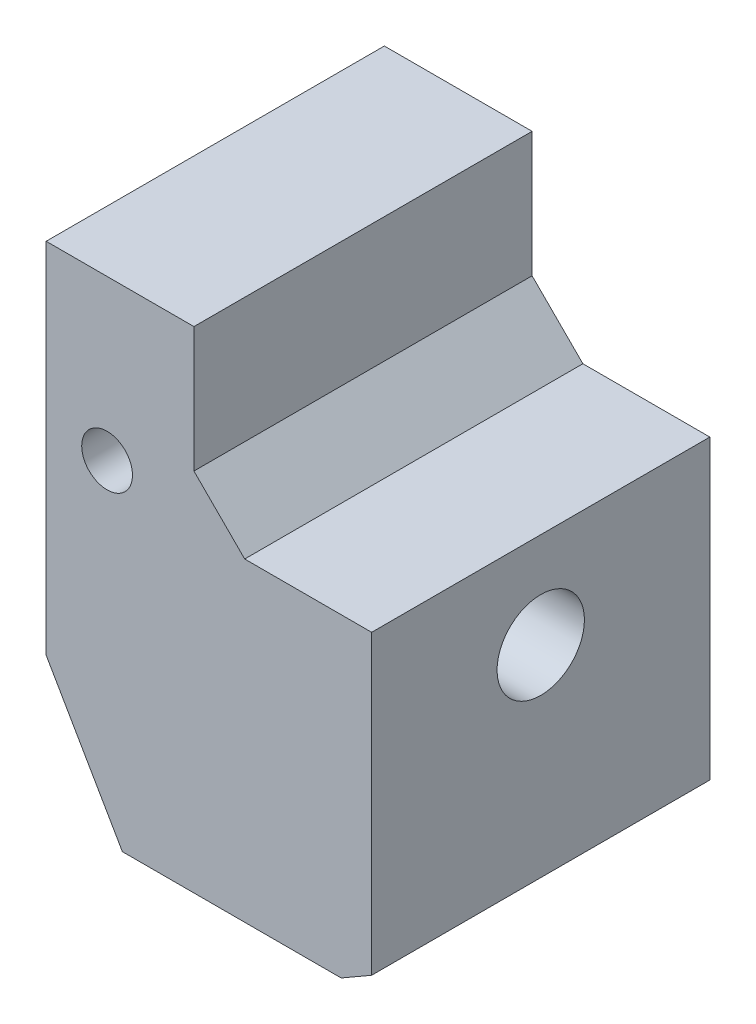
SolidWorks part; units mm, degrees
ref_plane "Front Plane" through (0, 0, 0) normal (0, 0, 1) x (1, 0, 0)
ref_plane "Top Plane" through (0, 0, 0) normal (0, 1, 0) x (1, 0, 0)
ref_plane "Right Plane" through (0, 0, 0) normal (1, 0, 0) x (0, 0, -1)
sketch "Sketch1" plane through (0, 0, 0) normal (1, 0, 0) x (0, 0, -1)
  line L1 (-16.65, 24.15) -> (16.65, 24.15)
  line L2 (-16.65, 24.15) -> (-16.65, -24.15)
  line L3 (-16.65, -24.15) -> (16.65, -24.15)
  line L4 (16.65, 24.15) -> (16.65, -24.15)
  line L5 (-16.65, 24.15) -> (16.65, -24.15) construction
  line L6 (-16.65, -24.15) -> (16.65, 24.15) construction
  point P0 (0, 0)
  dimension "D1" = 48.3
  dimension "D2" = 33.3
extrude "Boss-Extrude1" add sketch "Sketch1" along normal blind 9.55
sketch "Sketch2" plane through (0, 0, 0) normal (-1, 0, 0) x (0, 0, 1)
  line L0 (0, 24.15) -> (0, 19.15) construction
  line L1 (-4.5, 12.6332) -> (-4.5, 19.15)
  line L2 (-4.5, 12.6332) -> (-5.65, 11.45)
  line L3 (-16.65, 24.15) -> (16.65, 24.15) construction
  line L4 (0, 19.15) -> (0, -19.451) construction
  line L5 (0, -19.451) -> (0, -24.15) construction
  line L6 (16.65, -24.15) -> (-16.65, -24.15) construction
  line L7 (4.5, 19.15) -> (5.65, 19.15)
  line L8 (-11.65, -9.1) -> (-11.65, -0.8374)
  line L9 (-11.65, -9.95) -> (11.65, -9.95)
  line L10 (-5.5, 13.0391) -> (-5.5, 20.15)
  line L11 (4.5, 20.15) -> (-5.5, 20.15)
  line L12 (-11.65, -9.95) -> (-11.65, -9.1)
  line L13 (4.5, 20.15) -> (6.65, 20.15)
  line L14 (11.65, -9.95) -> (11.65, -9.1)
  line L15 (6.65, 20.15) -> (6.65, 5.9938)
  line L16 (6.65, 5.9938) -> (12.65, -0.4436)
  line L17 (12.65, -0.4436) -> (12.65, -9.1)
  line L18 (12.65, -10.95) -> (12.65, -9.1)
  line L19 (4.5, 19.15) -> (-4.5, 19.15)
  line L20 (-5.65, 5.6) -> (-5.65, 11.45)
  line L21 (-5.65, 5.6) -> (-11.65, -0.8374)
  line L22 (-12.65, -10.95) -> (12.65, -10.95)
  line L23 (-12.65, -10.95) -> (-12.65, -9.1)
  line L24 (-12.65, -9.1) -> (-12.65, -0.4436)
  line L25 (11.65, -0.8374) -> (11.65, -9.1)
  line L26 (5.65, 5.6) -> (11.65, -0.8374)
  line L27 (5.65, 19.15) -> (5.65, 5.6)
  line L28 (-6.65, 5.9938) -> (-12.65, -0.4436)
  line L29 (-6.65, 5.9938) -> (-6.65, 11.8559)
  line L30 (-5.5, 13.0391) -> (-6.65, 11.8559)
  point P16 (0, -10.1)
  dimension "D1" = 5
  dimension "D2" = 4.699
  dimension "D3" = 23.3
  dimension "D4" = 15.55
  dimension "D5" = 11.3
  dimension "D6" = 1.65
  dimension "D7" = 8.8
  dimension "D8" = 13.55
  dimension "D9" = 1
  dimension "D11" = 4.5
extrude "Cut-Extrude1" cut sketch "Sketch2" against normal blind 5.5 contours L27 L7 L19 L1 L2 L20 L21 L8 L12 L9 L14 L25 L26 | L10 L30 L29 L28 L24 L23 L22 L18 L17 L16 L15 L13 L11 L7 L27 L26 L25 L14 L9 L12 L8 L21 L20 L2 L1 L19 region at (0, 1.8051, 0.0888) region at (0, 16.5946, -5.0991)
sketch "Sketch3" plane through (5.5, 0, 0) normal (-1, 0, 0) x (0, 0, 1)
  line L0 (5.65, 19.15) -> (-4.5, 19.15)
  line L1 (-5.65, 5.45) -> (5.65, 5.45)
  line L2 (-5.65, 11.45) -> (-4.5, 12.6332)
  line L3 (-4.5, 12.6332) -> (-4.5, 19.15)
  line L4 (-5.65, 11.45) -> (-5.65, 5.45)
  line L5 (6.65, 20.15) -> (-5.5, 20.15)
  line L6 (0, 5.45) -> (0, 19.15) construction
  line L7 (-5.5, 13.0391) -> (-5.5, 20.15)
  line L8 (-6.65, 11.8559) -> (-5.5, 13.0391)
  line L9 (-6.65, 11.8559) -> (-6.65, 5.45)
  line L11 (5.65, 5.45) -> (5.65, 19.15)
  line L12 (6.65, 5.45) -> (6.65, 20.15)
  line L13 (-5.65, 5.45) -> (-6.65, 5.45)
  line L14 (5.65, 5.45) -> (6.65, 5.45)
  line L15 (-6.65, 11.8559) -> (-6.65, 4.45) construction
  line L16 (-6.65, 4.45) -> (6.65, 4.45) construction
  line L17 (6.65, 4.45) -> (6.65, 20.15) construction
  dimension "D2" = 5.45
  dimension "D3" = 5.65
  dimension "D4" = 13.7
  dimension "D5" = 6
  dimension "D6" = 4.5
  dimension "D7" = 135.816
  dimension "D8" = 5.45
  dimension "D1" = 1
extrude "Cut-Extrude2" cut sketch "Sketch3" against normal blind 5 contours L6 L1 L11 L0 | L1 L6 L0 L3 L2 L4 | L12 L5 L7 L8 L9 L11 L1 L4 L2 L3 L0 region at (5.5, 12.1167, 0.2838) region at (5.5, 19.3482, 0.575)
sketch "Sketch5" plane through (9.55, 0, 0) normal (1, 0, 0) x (0, 0, -1)
  line L1 (-16.65, 24.15) -> (16.65, 24.15)
  line L2 (-16.65, 24.15) -> (-16.65, -24.15)
  line L3 (-16.65, -24.15) -> (16.65, -24.15)
  line L4 (16.65, 24.15) -> (16.65, -24.15)
  line L5 (-16.65, 24.15) -> (16.65, -24.15) construction
  line L6 (-16.65, -24.15) -> (16.65, 24.15) construction
  point P0 (0, 0)
extrude "Boss-Extrude3" add sketch "Sketch5" along normal blind 22.5
sketch "Sketch6" plane through (5.5, 0, 0) normal (-1, 0, 0) x (0, 0, 1)
  line L0 (0, 5.45) -> (0, -2.575) construction
  line L2 (0, 1.45) -> (5.4752, 1.45) construction
  line L3 (-6.65, 5.45) -> (6.65, 5.45) construction
  circle A0 centre (0, -2.575) radius 4.025
  dimension "D2" = 8.05
  dimension "D1" = 4
  dimension "D3" = 8.025
extrude "Cut-Extrude3" cut sketch "Sketch6" against normal blind 12
sketch "Sketch7" plane through (17.5, 0, 0) normal (-1, 0, 0) x (0, 0, 1)
  circle A0 centre (0, -2.575) radius 4.3
  dimension "D1" = 8.6
extrude "Cut-Extrude4" cut sketch "Sketch7" against normal up to surface (14.55 mm away) up to face at (32.05, 0, 0)
sketch "Sketch27" plane through (0, 0, 5.65) normal (0, 0, -1) x (-1, 0, 0)
  line L1 (-9.55, 5.45) -> (-5.5, 5.45) construction
  circle A0 centre (-6, 8.45) radius 2.5
  dimension "D1" = 5
  dimension "D2" = 6
  dimension "D3" = 3
extrude "Cut-Extrude6" cut sketch "Sketch27" against normal through all both and the other way through all
ref_plane "Plane1" through (18.4698, -31.9906, 0) normal (0.5, -0.866, 0) x (0, 0, -1)
sketch "Sketch28" plane through (0, 0, 0) normal (0, 0, 1) x (1, 0, 0)
  line L0 (32.05, -2.575) -> (17.5, -2.575) construction
  line L1 (32.05, -6.875) -> (32.05, 1.725) construction
  line L2 (17.5, -6.6) -> (17.5, 1.45) construction
  line L3 (17.5, -2.575) -> (17.5, -6.6) construction
  line L4 (17.5, -6.875) -> (17.5, 1.725) construction
  line L5 (17.5, -6.6) -> (13.5, -6.6) construction
  line L6 (13.5, -6.6) -> (25.7369, -27.7949)
  line L7 (6.7789, -38.7403) -> (30.1606, -25.2408) construction
  line L8 (13.5, -6.6) -> (11.25, -2.7029)
  dimension "D1" = 4.025
  dimension "D2" = 4
  dimension "D3" = 60
  dimension "D4" = 180
  dimension "D5" = 4.5
sketch "Sketch29" plane through (0, 0, 0) normal (0, 0, 1) x (1, 0, 0)
  line L0 (32.05, -2.575) -> (17.5, -2.575) construction
  line L1 (32.05, -6.875) -> (32.05, 1.725) construction
  line L2 (19.5, -16.9923) -> (25.7369, -27.7949)
  line L3 (17.5, -2.575) -> (17.5, -6.6) construction
  line L4 (6.7789, -38.7403) -> (30.1606, -25.2408) construction
  line L5 (17.5, -6.6) -> (13.5, -6.6) construction
  line L6 (13.5, -6.6) -> (19.5, -16.9923) construction
  line L8 (13.5, -6.6) -> (25.7369, -27.7949) construction
  dimension "D1" = 4.025
  dimension "D2" = 4
  dimension "D3" = 12
  dimension "D4" = 60
sketch "Sketch30" plane through (18.4698, -31.9906, 0) normal (0.5, -0.866, 0) x (0, 0, -1)
  circle A0 centre (0, 8.3913) radius 4
  dimension "D1" = 8
sweep "Cut-Sweep1" cut profiles "Sketch30" path "Sketch28"
sketch "Sketch31" plane through (18.4698, -31.9906, 0) normal (0.5, -0.866, 0) x (0, 0, -1)
  circle A0 centre (0, 8.3913) radius 5.5
  dimension "D1" = 11
sweep "Cut-Sweep2" cut profiles "Sketch31" path "Sketch29"
chamfer "Chamfer1" distance 13 angle 30 1 edges at (0, -24.15, 0) first distance on face at (0, 0, 0)
chamfer "Chamfer2" distance 10 angle 60 1 edges at (32.05, 24.15, 0) first distance on face at (16.025, 24.15, 0)
chamfer "Chamfer3" distance 3 angle 30 1 edges at (32.05, -24.15, 0) first distance on face at (29.9834, -24.15, 0)
sketch "Croquis2" plane through (0, 0, 16.65) normal (0, 0, 1) x (1, 0, 0)
  line L0 (32.05, 6.8295) -> (14.55, 6.8295)
  line L1 (14.55, 6.8295) -> (14.55, 24.15)
  line L2 (22.05, 24.15) -> (0, 24.15) construction
  line L3 (14.55, 24.15) -> (32.05, 24.15)
  line L4 (32.05, 24.15) -> (32.05, 6.8295)
  dimension "D1" = 17.5
  dimension "D2" = 17.5
extrude "Cortar-Extruir1" cut sketch "Croquis2" against normal blind 48
chamfer "Chamfer4" distance 5 angle 45 1 edges at (14.55, 6.8295, 0)
sketch "Sketch33" plane through (0, 0, 0) normal (-1, 0, 0) x (0, 0, 1)
  line L0 (0, -9.95) -> (0, -15.45)
  line L2 (0, -15.45) -> (2.5, -15.45)
  line L3 (2.5, -15.45) -> (2.5, -9.95)
  line L5 (2.5, -9.95) -> (0, -9.95)
  line L6 (-12.65, -10.95) -> (12.65, -10.95) construction
  dimension "D1" = 5.5
  dimension "D2" = 2.5
  dimension "D3" = 1
sketch "Sketch34" plane through (5.5, 0, 0) normal (-1, 0, 0) x (0, 0, 1)
  line L0 (0, -9.95) -> (2.5, -9.95)
  line L2 (2.5, -9.95) -> (2.5, -10.45)
  line L3 (2.5, -10.45) -> (0, -10.45)
  line L4 (0, -10.45) -> (0, -9.95)
  line L5 (-12.65, -10.95) -> (12.65, -10.95) construction
  dimension "D1" = 0.5
  dimension "D2" = 1
  dimension "D3" = 2.5
loft "Cut-Loft2" cut profiles "Sketch33", "Sketch34" connector at (0, -15.45, 2.5) connector at (5.5, -10.45, 2.5)
